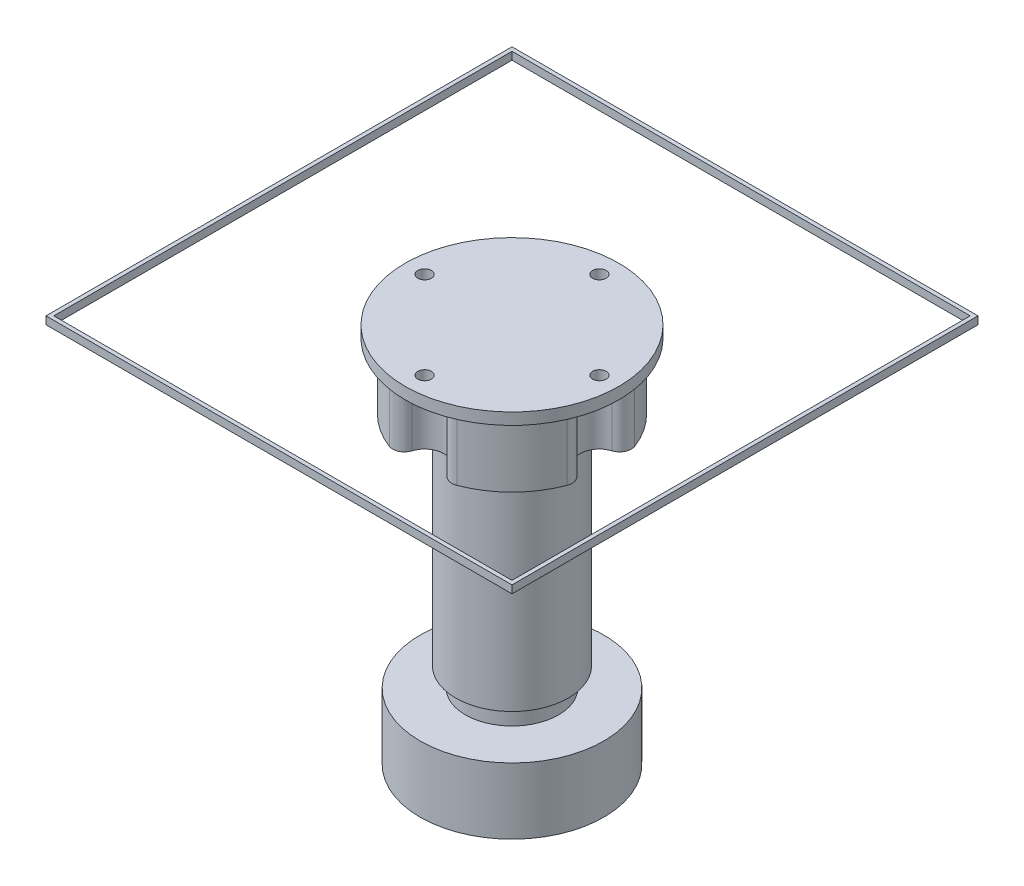
SolidWorks part; units mm, degrees
material "PE Высокой плотности"
ref_plane "Спереди" through (0, 0, 0) normal (0, 0, 1) x (1, 0, 0)
ref_plane "Сверху" through (0, 0, 0) normal (0, 1, 0) x (1, 0, 0)
ref_plane "Справа" through (0, 0, 0) normal (1, 0, 0) x (0, 0, -1)
sketch "Эскиз1" plane through (0, 0, 0) normal (0, 0, 1) x (1, 0, 0)
  line L0 (0, 0) -> (0, -13.7037) construction
  line L1 (0, 0) -> (-12, 0)
  line L2 (-12, 0) -> (-12, 2)
  line L3 (-12, 2) -> (-23.65, 2)
  line L4 (-23.65, 2) -> (-23.65, 19)
  line L5 (-23.65, 19) -> (-12, 19)
  line L6 (-12, 19) -> (-12, 24)
  line L7 (-12, 24) -> (-14.5, 24)
  line L8 (-14.5, 24) -> (-14.5, 80)
  line L9 (-14.5, 80) -> (-24.5, 80)
  line L10 (-24.5, 80) -> (-24.5, 97)
  line L11 (-24.5, 97) -> (-27.5, 97)
  line L12 (-27.5, 97) -> (-27.5, 100)
  line L13 (-27.5, 100) -> (0, 100)
  line L14 (0, 100) -> (0, 0)
  dimension "D1" = 24
  dimension "D2" = 47.3
  dimension "D3" = 29
  dimension "D4" = 49
  dimension "D5" = 55
  dimension "D6" = 100
  dimension "D7" = 2
  dimension "D8" = 17
  dimension "D9" = 76
  dimension "D10" = 3
  dimension "D11" = 20
revolve "Повернуть1" add sketch "Эскиз1" angle 360 about L0
sketch "Эскиз2" plane through (0, 100, 0) normal (0, 1, 0) x (1, 0, 0)
  circle A0 centre (0, 22.5) radius 1.75
  circle A1 centre (0, 0) radius 22.5 construction
  circle A2 centre (22.5, 0) radius 1.75
  circle A3 centre (0, -22.5) radius 1.75
  circle A4 centre (-22.5, 0) radius 1.75
  dimension "D1" = 45
  dimension "D2" = 3.5
extrude "Вырез-Вытянуть1" cut sketch "Эскиз2" against normal up to surface (20 mm away) up to face at (0, 80, 14.5)
sketch "Эскиз3" plane through (0, 80, 0) normal (0, -1, 0) x (1, 0, 0)
  circle A0 centre (0, 22.5) radius 5
  circle A1 centre (22.5, 0) radius 5
  circle A2 centre (0, -22.5) radius 5
  circle A3 centre (-22.5, 0) radius 5
  dimension "D1" = 10
extrude "Вырез-Вытянуть2" cut sketch "Эскиз3" against normal up to surface (17 mm away) up to face at (0, 97, 24.5)
fillet "Скругление1" radius 3 8 edges at (-24.0333, 88.5, 4.7591) (-24.0333, 88.5, -4.7591) (-4.7591, 88.5, -24.0333) (4.7591, 88.5, -24.0333) (24.0333, 88.5, 4.7591) (24.0333, 88.5, -4.7591) (-4.7591, 88.5, 24.0333) (4.7591, 88.5, 24.0333)
ref_plane "Плоскость1" through (0, 0, 60) normal (0, 0, 1) x (1, 0, 0)
ref_plane "Плоскость2" through (0, 0, -60) normal (0, 0, 1) x (1, 0, 0)
ref_plane "Плоскость3" through (60, 0, 0) normal (1, 0, 0) x (0, 0, -1)
ref_plane "Плоскость4" through (-60, 0, 0) normal (1, 0, 0) x (0, 0, -1)
sketch "Эскиз4" plane through (0, 100, 0) normal (0, 1, 0) x (1, 0, 0)
  line L1 (-60, -60) -> (60, -60)
  line L2 (-60, -60) -> (-60, 60)
  line L3 (-60, 60) -> (60, 60)
  line L4 (60, -60) -> (60, 60)
  line L5 (-60, -60) -> (60, 60) construction
  line L6 (-60, 60) -> (60, -60) construction
  line L7 (59, -59) -> (-59, -59)
  line L8 (59, -59) -> (59, 59)
  line L9 (59, 59) -> (-59, 59)
  line L10 (-59, -59) -> (-59, 59)
  line L11 (59, -59) -> (-59, 59) construction
  line L12 (59, 59) -> (-59, -59) construction
  point P0 (0, 0)
  point P6 (0, 0)
  dimension "D1" = 120
  dimension "D2" = 120
  dimension "D3" = 1
extrude "Бобышка-Вытянуть1" add sketch "Эскиз4" along normal blind 2 separate body
